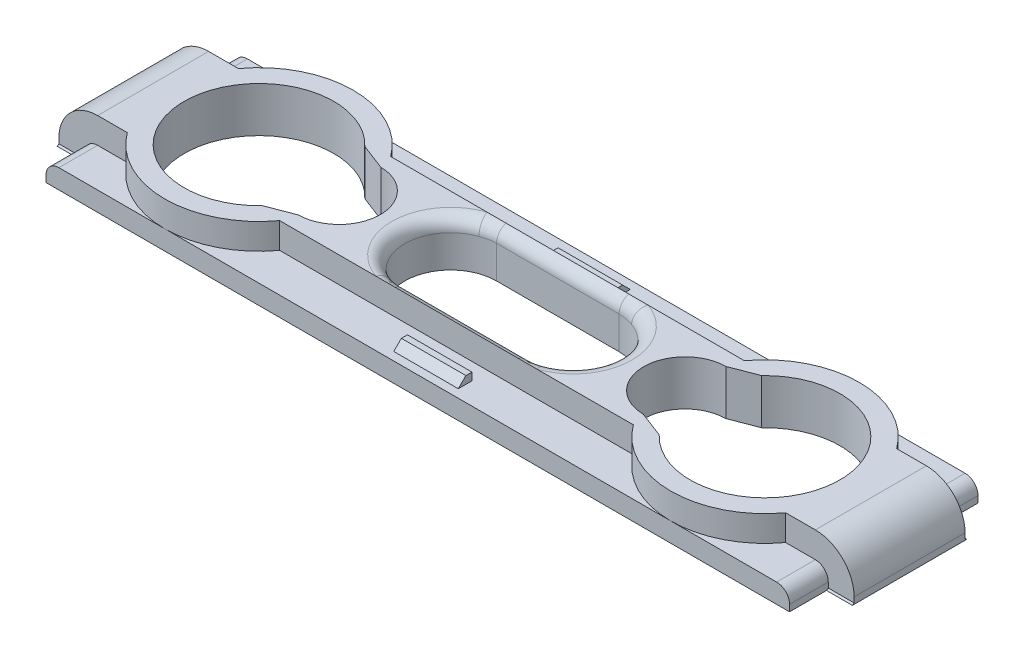
SolidWorks part; units mm, degrees
ref_plane "正面" through (0, 0, 0) normal (0, 0, 1) x (1, 0, 0)
ref_plane "平面" through (0, 0, 0) normal (0, 1, 0) x (1, 0, 0)
ref_plane "右側面" through (0, 0, 0) normal (1, 0, 0) x (0, 0, -1)
sketch "ｽｹｯﾁ2" plane through (0, 0, 0) normal (0, 0, 1) x (1, 0, 0)
  line L0 (0, 0) -> (54, 0) construction
  line L1 (0, 20) -> (54, 20) construction
  line L2 (-3.8, 47.4) -> (57.8, 47.4)
  line L3 (54, 0) -> (54, 40) construction
  line L4 (54, 40) -> (0, 40) construction
  line L5 (0, 40) -> (0, 0) construction
  line L6 (57.8, 47.4) -> (57.8, -7.4)
  line L7 (57.8, -7.4) -> (-3.8, -7.4)
  line L8 (-3.8, -7.4) -> (-3.8, 47.4)
  line L9 (27, 47.4) -> (27, -7.4) construction
  line L10 (27, 32.0981) -> (27, 34.8848) construction
  line L11 (17.3965, 32.0981) -> (17.3965, 34.8848)
  line L12 (36.6035, 32.0981) -> (36.6035, 34.8848)
  line L13 (27, 7.9019) -> (27, 5.1152) construction
  line L14 (17.3965, 7.9019) -> (17.3965, 5.1152)
  line L15 (36.6035, 7.9019) -> (36.6035, 5.1152)
  line L16 (52, 20) -> (27, 20) construction
  line L18 (46.1198, 20) -> (44.8536, 20) construction
  line L19 (52, 23.9649) -> (52, 16.0351) construction
  line L20 (46.1198, 13.1981) -> (44.8536, 13.1981)
  line L21 (46.1198, 26.8019) -> (44.8536, 26.8019)
  line L22 (7.8802, 20) -> (9.1464, 20) construction
  line L23 (7.8802, 13.1981) -> (9.1464, 13.1981)
  line L24 (7.8802, 26.8019) -> (9.1464, 26.8019)
  circle A0 centre (2, 2) radius 1.1 construction
  circle A1 centre (52, 2) radius 1.1 construction
  circle A2 centre (52, 38) radius 1.1 construction
  circle A3 centre (2, 38) radius 1.1 construction
  circle A4 centre (2, 38) radius 1.05
  circle A5 centre (2, 38) radius 1.8491
  circle A6 centre (2, 2) radius 1.8491
  circle A7 centre (52, 2) radius 1.8491
  circle A8 centre (52, 38) radius 1.8491
  circle A9 centre (52, 38) radius 1.05
  circle A10 centre (52, 2) radius 1.05
  circle A11 centre (2, 2) radius 1.05
  arc A12 (17.3965, 32.0981) -> (36.6035, 32.0981) centre (27, 32.0981) ccw
  arc A13 (36.6035, 34.8848) -> (17.3965, 34.8848) centre (27, 34.8848) ccw
  arc A14 (46.1198, 13.1981) -> (46.1198, 26.8019) centre (46.1198, 20) ccw
  arc A15 (44.8536, 26.8019) -> (44.8536, 13.1981) centre (44.8536, 20) ccw
  arc A16 (7.8802, 13.1981) -> (7.8802, 26.8019) centre (7.8802, 20) cw
  arc A17 (9.1464, 26.8019) -> (9.1464, 13.1981) centre (9.1464, 20) cw
  arc A18 (17.3965, 7.9019) -> (36.6035, 7.9019) centre (27, 7.9019) cw
  arc A19 (36.6035, 5.1152) -> (17.3965, 5.1152) centre (27, 5.1152) cw
  point P30 (27, 33.4915)
  point P41 (45.4867, 20)
  point P48 (8.5133, 20)
  point P55 (27, 6.5085)
  dimension "D3" = 2.2
  dimension "D8" = 2.1
  dimension "D9" = 30.8
  dimension "D1" = 40
  dimension "D2" = 54
  dimension "D4" = 27.4
  dimension "D5" = 27.4
extrude "ﾎﾞｽ - 押し出し1" add sketch "ｽｹｯﾁ2" along normal blind 1.5 contours L7 L8 L2 L6 | L15 A19 L14 A18 | L20 A15 L21 A14 | L11 A13 L12 A12 | A17 L23 A16 L24
extrude "ﾎﾞｽ - 押し出し3" add sketch "ｽｹｯﾁ2<4>" along normal blind 3.3 contours A7 | A6 | A5 | A8
sketch "ｽｹｯﾁ2<4>" plane through (0, 0, 0) normal (0, 0, 1) x (1, 0, 0) same geometry as "ｽｹｯﾁ2"
sketch "ｽｹｯﾁ6" plane through (-3.8, 0, 0) normal (-1, 0, 0) x (0, 0, 1)
  line L0 (1.5, -7.4) -> (0, -7.4) construction
  line L7 (1.5, -7.4) -> (1.5, 47.4) construction
  line L8 (-9.6, 33.9866) -> (-8.8, 31.9) construction
  line L9 (-5.8, 43.7) -> (-5.8, 19.9) construction
  line L12 (-13.1, 20) -> (0, 20) construction
  line L14 (-2.8, 31.9) -> (-2, 33.9866) construction
  line L15 (-9.6, 33.9866) -> (-8.8, 31.9) construction
  line L20 (-13.1, 47.4) -> (-13.1, -7.4)
  line L21 (1.5, -7.4) -> (1.5, 47.4)
  line L22 (-5.8, 23.1) -> (-5.8, 16.9) construction
  line L23 (-3.5215, 23.1) -> (-3.5215, 16.9)
  line L24 (-8.0785, 23.1) -> (-8.0785, 16.9)
  line L26 (1.5, 47.4) -> (-13.1, 47.4)
  line L27 (1.5, -7.4) -> (-13.1, -7.4)
  line L28 (-2.8, 31.9) -> (-2, 33.9866) construction
  line L29 (0, -7.4) -> (0, 47.4) construction
  line L30 (-2.8, 8.1) -> (-2, 6.0134) construction
  line L31 (-9.6, 6.0134) -> (-8.8, 8.1) construction
  line L32 (0, 16.9) -> (-11.6, 16.9) construction
  line L33 (-9.7702, 33.8718) -> (-8.9998, 31.8624)
  line L34 (-2.6002, 31.8624) -> (-1.8298, 33.8718)
  line L35 (-2.6002, 8.1376) -> (-1.8298, 6.1282)
  line L36 (-9.7702, 6.1282) -> (-8.9998, 8.1376)
  arc A3 (-2, 33.9866) -> (-9.6, 33.9866) centre (-5.8, 38.1) ccw construction
  arc A4 (-2, 33.9866) -> (-9.6, 33.9866) centre (-5.8, 38.1) ccw construction
  arc A10 (-8.8, 31.9) -> (-2.8, 31.9) centre (-5.8, 31.9) ccw construction
  arc A11 (-8.8, 31.9) -> (-2.8, 31.9) centre (-5.8, 31.9) ccw construction
  arc A12 (-3.5215, 23.1) -> (-8.0785, 23.1) centre (-5.8, 23.1) ccw
  arc A13 (-8.0785, 16.9) -> (-3.5215, 16.9) centre (-5.8, 16.9) ccw
  arc A14 (-8.8, 8.1) -> (-2.8, 8.1) centre (-5.8, 8.1) cw construction
  arc A15 (-2, 6.0134) -> (-9.6, 6.0134) centre (-5.8, 1.9) cw construction
  arc A16 (-1.8298, 33.8718) -> (-9.7702, 33.8718) centre (-5.8, 38.1) ccw
  arc A17 (-8.9998, 31.8624) -> (-2.6002, 31.8624) centre (-5.8, 31.9) ccw
  arc A18 (-8.9998, 8.1376) -> (-2.6002, 8.1376) centre (-5.8, 8.1) cw
  arc A19 (-1.8298, 6.1282) -> (-9.7702, 6.1282) centre (-5.8, 1.9) cw
  point P32 (-5.8, 20)
  dimension "D2" = 0.2
  dimension "D1" = 0
extrude "ﾎﾞｽ - 押し出し4" add sketch "ｽｹｯﾁ6" against normal up to surface (3.5 mm away)
sketch "ｽｹｯﾁ9" plane through (57.8, 0, 0) normal (1, 0, 0) x (0, 0, -1)
  line L2 (8.9998, 31.8624) -> (9.7702, 33.8718)
  line L3 (1.8298, 33.8718) -> (2.6002, 31.8624)
  line L4 (8.9998, 31.8624) -> (9.7702, 33.8718)
  line L5 (1.8298, 33.8718) -> (2.6002, 31.8624)
  line L6 (2.6002, 8.1376) -> (1.8298, 6.1282)
  line L7 (9.7702, 6.1282) -> (8.9998, 8.1376)
  line L8 (2.6002, 8.1376) -> (1.8298, 6.1282)
  line L9 (9.7702, 6.1282) -> (8.9998, 8.1376)
  line L10 (3.5215, 23.1) -> (3.5215, 16.9)
  line L11 (8.0785, 16.9) -> (8.0785, 23.1)
  line L12 (3.5215, 23.1) -> (3.5215, 16.9)
  line L13 (8.0785, 16.9) -> (8.0785, 23.1)
  line L16 (-1.5, 47.4) -> (-1.5, -7.4)
  line L17 (13.1, 47.4) -> (-1.5, 47.4)
  line L18 (13.1, -7.4) -> (13.1, 47.4)
  line L19 (-1.5, -7.4) -> (13.1, -7.4)
  line L20 (-1.5, 47.4) -> (-1.5, -7.4)
  line L21 (13.1, 47.4) -> (-1.5, 47.4)
  line L22 (13.1, -7.4) -> (13.1, 47.4)
  line L23 (-1.5, -7.4) -> (13.1, -7.4)
  arc A2 (2.6002, 31.8624) -> (8.9998, 31.8624) centre (5.8, 31.9) ccw
  arc A3 (9.7702, 33.8718) -> (1.8298, 33.8718) centre (5.8, 38.1) ccw
  arc A4 (2.6002, 31.8624) -> (8.9998, 31.8624) centre (5.8, 31.9) ccw
  arc A5 (9.7702, 33.8718) -> (1.8298, 33.8718) centre (5.8, 38.1) ccw
  arc A6 (1.8298, 6.1282) -> (9.7702, 6.1282) centre (5.8, 1.9) ccw
  arc A7 (8.9998, 8.1376) -> (2.6002, 8.1376) centre (5.8, 8.1) ccw
  arc A8 (1.8298, 6.1282) -> (9.7702, 6.1282) centre (5.8, 1.9) ccw
  arc A9 (8.9998, 8.1376) -> (2.6002, 8.1376) centre (5.8, 8.1) ccw
  arc A10 (3.5215, 16.9) -> (8.0785, 16.9) centre (5.8, 16.9) ccw
  arc A11 (8.0785, 23.1) -> (3.5215, 23.1) centre (5.8, 23.1) ccw
  arc A12 (3.5215, 16.9) -> (8.0785, 16.9) centre (5.8, 16.9) ccw
  arc A13 (8.0785, 23.1) -> (3.5215, 23.1) centre (5.8, 23.1) ccw
  dimension "D1" = 0
  dimension "D2" = 0
  dimension "D3" = 0
  dimension "D4" = 0
extrude "ﾎﾞｽ - 押し出し6" add sketch "ｽｹｯﾁ9" against normal up to surface (3.5 mm away)
sketch "ｽｹｯﾁ10" plane through (0, -7.4, 0) normal (0, -1, 0) x (1, 0, 0)
  line L0 (22.25, -5.8) -> (31.75, -5.8) construction
  line L1 (22.25, -2.25) -> (31.75, -2.25)
  line L2 (22.25, -9.35) -> (31.75, -9.35)
  line L5 (27, 1.5) -> (27, -13.1) construction
  line L10 (16.8, -5.8) -> (37.2, -5.8) construction
  line L11 (21.4, -5.8) -> (32.6, -5.8) construction
  line L13 (21.4, -2.55) -> (32.6, -2.55) construction
  line L14 (21.4, -9.05) -> (32.6, -9.05) construction
  line L17 (11.5134, -9.6) -> (13.6, -8.8)
  line L18 (57.8, 1.5) -> (57.8, -13.1) construction
  line L19 (57.8, 1.5) -> (-3.8, 1.5) construction
  line L20 (-3.8, 1.5) -> (-3.8, -13.1) construction
  line L22 (13.6, -2.8) -> (11.5134, -2)
  line L23 (57.8, 1.5) -> (57.8, -13.1)
  line L24 (57.8, 1.5) -> (-3.8, 1.5)
  line L25 (-3.8, 1.5) -> (-3.8, -13.1)
  line L27 (11.5134, -9.6) -> (13.6, -8.8) construction
  line L28 (13.6, -2.8) -> (11.5134, -2) construction
  line L29 (-3.8, -13.1) -> (57.8, -13.1)
  line L46 (11.6282, -9.7702) -> (13.6376, -8.9998)
  line L47 (13.6376, -2.6002) -> (11.6282, -1.8298)
  line L48 (40.4, -2.8) -> (42.4866, -2) construction
  line L49 (42.4866, -9.6) -> (40.4, -8.8) construction
  line L50 (40.3624, -2.6002) -> (42.3718, -1.8298)
  line L51 (42.3718, -9.7702) -> (40.3624, -8.9998)
  arc A1 (22.25, -2.25) -> (22.25, -9.35) centre (22.25, -5.8) ccw
  arc A2 (31.75, -9.35) -> (31.75, -2.25) centre (31.75, -5.8) ccw
  arc A8 (21.4, -2.55) -> (21.4, -9.05) centre (21.4, -5.8) ccw construction
  arc A9 (32.6, -9.05) -> (32.6, -2.55) centre (32.6, -5.8) ccw construction
  arc A12 (11.5134, -2) -> (11.5134, -9.6) centre (7.4, -5.8) ccw
  arc A13 (13.6, -8.8) -> (13.6, -2.8) centre (13.6, -5.8) ccw
  arc A14 (11.5134, -2) -> (11.5134, -9.6) centre (7.4, -5.8) ccw construction
  arc A15 (13.6, -8.8) -> (13.6, -2.8) centre (13.6, -5.8) ccw construction
  arc A32 (11.6282, -1.8298) -> (11.6282, -9.7702) centre (7.4, -5.8) ccw
  arc A33 (13.6376, -8.9998) -> (13.6376, -2.6002) centre (13.6, -5.8) ccw
  arc A34 (40.4, -8.8) -> (40.4, -2.8) centre (40.4, -5.8) cw construction
  arc A35 (42.4866, -2) -> (42.4866, -9.6) centre (46.6, -5.8) cw construction
  arc A36 (40.3624, -8.9998) -> (40.3624, -2.6002) centre (40.4, -5.8) cw
  arc A37 (42.3718, -1.8298) -> (42.3718, -9.7702) centre (46.6, -5.8) cw
  point P24 (27, -5.8)
  point P41 (27, -5.8)
  dimension "D1" = 0
  dimension "D4" = 11.2
  dimension "D2" = 0.2
  dimension "D3" = 6.5
extrude "ﾎﾞｽ - 押し出し7" add sketch "ｽｹｯﾁ10" against normal blind 3.5
sketch "ｽｹｯﾁ11" plane through (0, 47.4, 0) normal (0, 1, 0) x (1, 0, 0)
  line L2 (40.3624, 2.6002) -> (42.3718, 1.8298)
  line L3 (42.3718, 9.7702) -> (40.3624, 8.9998)
  line L4 (57.8, -1.5) -> (57.8, 13.1)
  line L5 (57.8, 13.1) -> (-3.8, 13.1)
  line L6 (-3.8, 13.1) -> (-3.8, -1.5)
  line L7 (-3.8, -1.5) -> (57.8, -1.5)
  line L8 (57.8, -1.5) -> (57.8, 13.1)
  line L9 (57.8, 13.1) -> (-3.8, 13.1)
  line L10 (-3.8, 13.1) -> (-3.8, -1.5)
  line L11 (-3.8, -1.5) -> (57.8, -1.5)
  line L12 (40.3624, 2.6002) -> (42.3718, 1.8298)
  line L13 (42.3718, 9.7702) -> (40.3624, 8.9998)
  line L14 (13.6376, 8.9998) -> (11.6282, 9.7702)
  line L15 (11.6282, 1.8298) -> (13.6376, 2.6002)
  line L16 (13.6376, 8.9998) -> (11.6282, 9.7702)
  line L17 (11.6282, 1.8298) -> (13.6376, 2.6002)
  line L18 (22.25, 2.25) -> (31.75, 2.25)
  line L19 (31.75, 9.35) -> (22.25, 9.35)
  line L20 (22.25, 2.25) -> (31.75, 2.25)
  line L21 (31.75, 9.35) -> (22.25, 9.35)
  arc A2 (42.3718, 1.8298) -> (42.3718, 9.7702) centre (46.6, 5.8) ccw
  arc A3 (40.3624, 8.9998) -> (40.3624, 2.6002) centre (40.4, 5.8) ccw
  arc A4 (42.3718, 1.8298) -> (42.3718, 9.7702) centre (46.6, 5.8) ccw
  arc A5 (40.3624, 8.9998) -> (40.3624, 2.6002) centre (40.4, 5.8) ccw
  arc A6 (13.6376, 2.6002) -> (13.6376, 8.9998) centre (13.6, 5.8) ccw
  arc A7 (11.6282, 9.7702) -> (11.6282, 1.8298) centre (7.4, 5.8) ccw
  arc A8 (13.6376, 2.6002) -> (13.6376, 8.9998) centre (13.6, 5.8) ccw
  arc A9 (11.6282, 9.7702) -> (11.6282, 1.8298) centre (7.4, 5.8) ccw
  arc A10 (31.75, 2.25) -> (31.75, 9.35) centre (31.75, 5.8) ccw
  arc A11 (22.25, 9.35) -> (22.25, 2.25) centre (22.25, 5.8) ccw
  arc A12 (31.75, 2.25) -> (31.75, 9.35) centre (31.75, 5.8) ccw
  arc A13 (22.25, 9.35) -> (22.25, 2.25) centre (22.25, 5.8) ccw
  dimension "D1" = 0
  dimension "D2" = 0
  dimension "D3" = 0
  dimension "D4" = 0
extrude "ﾎﾞｽ - 押し出し8" add sketch "ｽｹｯﾁ11" against normal blind 3.5
fillet "ﾌｨﾚｯﾄ1" radius 3 4 edges at (-3.8, -7.4, -5.8) (57.8, -7.4, -5.8) (57.8, 47.4, -5.8) (-3.8, 47.4, -5.8)
sketch "ｽｹｯﾁ12" plane through (0, 0, -13.1) normal (0, 0, -1) x (-1, 0, 0)
  line L1 (-55.8, 44.4) -> (-55.8, -4.4)
  line L2 (-54.8, -5.4) -> (0.8, -5.4)
  line L3 (1.8, -4.4) -> (1.8, 44.4)
  line L4 (-54.8, -7.4) -> (0.8, -7.4)
  line L5 (3.8, -4.4) -> (3.8, 44.4)
  line L6 (-54.8, -7.4) -> (0.8, -7.4)
  line L7 (-57.8, 44.4) -> (-57.8, -4.4)
  line L8 (0.8, 47.4) -> (-54.8, 47.4)
  line L9 (3.8, -4.4) -> (3.8, 44.4)
  line L10 (0.8, 47.4) -> (-54.8, 47.4)
  line L11 (-57.8, 44.4) -> (-57.8, -4.4)
  line L12 (0.8, 45.4) -> (-54.8, 45.4)
  line L16 (-57.8, 44.4) -> (-57.8, -4.4) construction
  line L17 (-54.8, -7.4) -> (0.8, -7.4) construction
  line L18 (0.8, 47.4) -> (-54.8, 47.4) construction
  arc A0 (-54.8, 45.4) -> (-55.8, 44.4) centre (-54.8, 44.4) ccw
  arc A1 (-55.8, -4.4) -> (-54.8, -5.4) centre (-54.8, -4.4) ccw
  arc A2 (0.8, -5.4) -> (1.8, -4.4) centre (0.8, -4.4) ccw
  arc A3 (1.8, 44.4) -> (0.8, 45.4) centre (0.8, 44.4) ccw
  arc A4 (0.8, -7.4) -> (3.8, -4.4) centre (0.8, -4.4) ccw
  arc A5 (3.8, 44.4) -> (0.8, 47.4) centre (0.8, 44.4) ccw
  arc A6 (-54.8, 47.4) -> (-57.8, 44.4) centre (-54.8, 44.4) ccw
  arc A7 (-57.8, -4.4) -> (-54.8, -7.4) centre (-54.8, -4.4) ccw
  arc A8 (0.8, -7.4) -> (3.8, -4.4) centre (0.8, -4.4) ccw
  arc A9 (3.8, 44.4) -> (0.8, 47.4) centre (0.8, 44.4) ccw
  arc A10 (-54.8, 47.4) -> (-57.8, 44.4) centre (-54.8, 44.4) ccw
  arc A11 (-57.8, -4.4) -> (-54.8, -7.4) centre (-54.8, -4.4) ccw
  dimension "D1" = 0
  dimension "D2" = 2
extrude "ｶｯﾄ - 押し出し1" cut sketch "ｽｹｯﾁ12" against normal blind 3
sketch "ｽｹｯﾁ22" plane through (0, 0, 1.5) normal (0, 0, 1) x (1, 0, 0)
  line L0 (-1.8, 44.4) -> (-1.8, -4.4)
  line L1 (-0.8, -5.4) -> (54.8, -5.4)
  line L2 (55.8, -4.4) -> (55.8, 44.4)
  line L3 (54.8, 45.4) -> (-0.8, 45.4)
  line L4 (-3.8, 44.4) -> (-3.8, -4.4)
  line L5 (-0.8, -7.4) -> (54.8, -7.4)
  line L6 (57.8, -4.4) -> (57.8, 44.4)
  line L7 (54.8, 47.4) -> (-0.8, 47.4)
  line L8 (-3.8, 44.4) -> (-3.8, -4.4)
  line L9 (-0.8, -7.4) -> (54.8, -7.4)
  line L10 (57.8, -4.4) -> (57.8, 44.4)
  line L11 (54.8, 47.4) -> (-0.8, 47.4)
  arc A0 (-1.8, -4.4) -> (-0.8, -5.4) centre (-0.8, -4.4) ccw
  arc A1 (54.8, -5.4) -> (55.8, -4.4) centre (54.8, -4.4) ccw
  arc A2 (55.8, 44.4) -> (54.8, 45.4) centre (54.8, 44.4) ccw
  arc A3 (-0.8, 45.4) -> (-1.8, 44.4) centre (-0.8, 44.4) ccw
  arc A4 (-3.8, -4.4) -> (-0.8, -7.4) centre (-0.8, -4.4) ccw
  arc A5 (54.8, -7.4) -> (57.8, -4.4) centre (54.8, -4.4) ccw
  arc A6 (57.8, 44.4) -> (54.8, 47.4) centre (54.8, 44.4) ccw
  arc A7 (-0.8, 47.4) -> (-3.8, 44.4) centre (-0.8, 44.4) ccw
  arc A8 (-3.8, -4.4) -> (-0.8, -7.4) centre (-0.8, -4.4) ccw
  arc A9 (54.8, -7.4) -> (57.8, -4.4) centre (54.8, -4.4) ccw
  arc A10 (57.8, 44.4) -> (54.8, 47.4) centre (54.8, 44.4) ccw
  arc A11 (-0.8, 47.4) -> (-3.8, 44.4) centre (-0.8, 44.4) ccw
  dimension "D1" = 0
  dimension "D2" = 2
extrude "ｶｯﾄ - 押し出し2" cut sketch "ｽｹｯﾁ22" against normal blind 3
sketch "ｽｹｯﾁ21" plane through (0, -7.4, 0) normal (0, -1, 0) x (1, 0, 0)
  line L0 (-0.8, -5.8) -> (-7.911, -5.8) construction
  line L1 (11.2923, -1.5) -> (42.7077, -1.5) construction
  line L5 (1.5008, -10.1) -> (3.5077, -10.1)
  line L6 (-0.8, -1.5) -> (3.5077, -1.5) construction
  line L10 (11.2923, -1.5) -> (13.2992, -1.5)
  line L11 (-0.8, -1.5) -> (-0.8, -10.1) construction
  line L12 (1.5008, -1.5) -> (3.5077, -1.5)
  line L19 (11.2923, -10.1) -> (13.2992, -10.1)
  line L23 (27, 1.5) -> (27, 9.2892) construction
  line L24 (-0.8, 1.5) -> (54.8, 1.5) construction
  line L25 (42.7077, -10.1) -> (40.7008, -10.1)
  line L26 (52.4992, -1.5) -> (50.4923, -1.5)
  line L27 (42.7077, -1.5) -> (40.7008, -1.5)
  line L28 (52.4992, -10.1) -> (50.4923, -10.1)
  arc A6 (13.2992, -10.1) -> (1.5008, -10.1) centre (7.4, -5.8) cw
  arc A10 (11.2923, -1.5) -> (3.5077, -1.5) centre (7.4, -5.8) ccw construction
  arc A13 (11.2923, -1.5) -> (3.5077, -1.5) centre (7.4, -5.8) ccw
  arc A14 (13.2992, -1.5) -> (1.5008, -1.5) centre (7.4, -5.8) ccw
  arc A25 (12.2989, -0.3879) -> (2.5011, -0.3879) centre (7.4, -5.8) ccw construction
  arc A26 (11.2923, -10.1) -> (3.5077, -10.1) centre (7.4, -5.8) cw
  arc A27 (42.7077, -10.1) -> (50.4923, -10.1) centre (46.6, -5.8) ccw
  arc A28 (40.7008, -1.5) -> (52.4992, -1.5) centre (46.6, -5.8) cw
  arc A29 (42.7077, -1.5) -> (50.4923, -1.5) centre (46.6, -5.8) cw
  arc A30 (40.7008, -10.1) -> (52.4992, -10.1) centre (46.6, -5.8) ccw
  dimension "D1" = 1.5
extrude "ﾎﾞｽ - 押し出し9" add sketch "ｽｹｯﾁ21" against normal up to surface (2 mm away) up to face at (27, -5.4, -0.375)
sketch "ｽｹｯﾁ23" plane through (0, 47.4, 0) normal (0, 1, 0) x (1, 0, 0)
  line L2 (1.5008, 10.1) -> (3.5077, 10.1)
  line L3 (11.2923, 10.1) -> (13.2992, 10.1)
  line L4 (1.5008, 10.1) -> (3.5077, 10.1)
  line L5 (11.2923, 10.1) -> (13.2992, 10.1)
  line L6 (52.4992, 1.5) -> (50.4923, 1.5)
  line L7 (42.7077, 1.5) -> (40.7008, 1.5)
  line L8 (52.4992, 1.5) -> (50.4923, 1.5)
  line L9 (42.7077, 1.5) -> (40.7008, 1.5)
  line L10 (40.7008, 10.1) -> (42.7077, 10.1)
  line L11 (50.4923, 10.1) -> (52.4992, 10.1)
  line L12 (40.7008, 10.1) -> (42.7077, 10.1)
  line L13 (50.4923, 10.1) -> (52.4992, 10.1)
  line L14 (13.2992, 1.5) -> (11.2923, 1.5)
  line L15 (3.5077, 1.5) -> (1.5008, 1.5)
  line L16 (13.2992, 1.5) -> (11.2923, 1.5)
  line L17 (3.5077, 1.5) -> (1.5008, 1.5)
  arc A2 (11.2923, 10.1) -> (3.5077, 10.1) centre (7.4, 5.8) ccw
  arc A3 (13.2992, 10.1) -> (1.5008, 10.1) centre (7.4, 5.8) ccw
  arc A4 (11.2923, 10.1) -> (3.5077, 10.1) centre (7.4, 5.8) ccw
  arc A5 (13.2992, 10.1) -> (1.5008, 10.1) centre (7.4, 5.8) ccw
  arc A6 (42.7077, 1.5) -> (50.4923, 1.5) centre (46.6, 5.8) ccw
  arc A7 (40.7008, 1.5) -> (52.4992, 1.5) centre (46.6, 5.8) ccw
  arc A8 (42.7077, 1.5) -> (50.4923, 1.5) centre (46.6, 5.8) ccw
  arc A9 (40.7008, 1.5) -> (52.4992, 1.5) centre (46.6, 5.8) ccw
  arc A10 (52.4992, 10.1) -> (40.7008, 10.1) centre (46.6, 5.8) ccw
  arc A11 (50.4923, 10.1) -> (42.7077, 10.1) centre (46.6, 5.8) ccw
  arc A12 (52.4992, 10.1) -> (40.7008, 10.1) centre (46.6, 5.8) ccw
  arc A13 (50.4923, 10.1) -> (42.7077, 10.1) centre (46.6, 5.8) ccw
  arc A14 (1.5008, 1.5) -> (13.2992, 1.5) centre (7.4, 5.8) ccw
  arc A15 (3.5077, 1.5) -> (11.2923, 1.5) centre (7.4, 5.8) ccw
  arc A16 (1.5008, 1.5) -> (13.2992, 1.5) centre (7.4, 5.8) ccw
  arc A17 (3.5077, 1.5) -> (11.2923, 1.5) centre (7.4, 5.8) ccw
  dimension "D1" = 0
  dimension "D2" = 0
  dimension "D3" = 0
  dimension "D4" = 0
extrude "ﾎﾞｽ - 押し出し10" add sketch "ｽｹｯﾁ23" against normal up to surface (2 mm away) up to face at (27, 45.4, -11.225)
sketch "ｽｹｯﾁ24" plane through (57.8, 0, 0) normal (1, 0, 0) x (0, 0, -1)
  line L0 (1.5, 5.7923) -> (1.5, 34.2077) construction
  line L1 (1.5, 41.9923) -> (1.5, 44.4) construction
  line L3 (1.5, 41.9923) -> (1.5, 43.9992)
  line L4 (1.5, 32.2008) -> (1.5, 34.2077)
  line L7 (5.8, 44.4) -> (5.8, 52.6929) construction
  line L8 (10.1, 44.4) -> (1.5, 44.4) construction
  line L9 (10.1, 32.2008) -> (10.1, 34.2077)
  line L10 (10.1, 41.9923) -> (10.1, 43.9992)
  line L11 (-1.5, 20) -> (-9.7166, 20) construction
  line L15 (-1.5, -4.4) -> (-1.5, 44.4) construction
  line L22 (10.1, -1.9923) -> (10.1, -3.9992)
  line L23 (10.1, 7.7992) -> (10.1, 5.7923)
  line L24 (1.5, 7.7992) -> (1.5, 5.7923)
  line L25 (1.5, -1.9923) -> (1.5, -3.9992)
  arc A0 (1.5, 43.9992) -> (1.5, 32.2008) centre (5.8, 38.1) ccw
  arc A1 (0.3879, 42.9989) -> (0.3879, 33.2011) centre (5.8, 38.1) ccw construction
  arc A7 (1.5, 41.9923) -> (1.5, 34.2077) centre (5.8, 38.1) ccw construction
  arc A11 (1.5, 41.9923) -> (1.5, 34.2077) centre (5.8, 38.1) ccw
  arc A12 (10.1, 43.9992) -> (10.1, 32.2008) centre (5.8, 38.1) cw
  arc A13 (10.1, -3.9992) -> (10.1, 7.7992) centre (5.8, 1.9) ccw
  arc A14 (1.5, -1.9923) -> (1.5, 5.7923) centre (5.8, 1.9) cw
  arc A15 (1.5, -3.9992) -> (1.5, 7.7992) centre (5.8, 1.9) cw
  arc A16 (10.1, 34.2077) -> (10.1, 41.9923) centre (5.8, 38.1) ccw construction
  arc A17 (10.1, -1.9923) -> (10.1, 5.7923) centre (5.8, 1.9) ccw construction
  arc A18 (10.1, 34.2077) -> (10.1, 41.9923) centre (5.8, 38.1) ccw
  arc A19 (10.1, -1.9923) -> (10.1, 5.7923) centre (5.8, 1.9) ccw
  dimension "D1" = 1.5
extrude "ﾎﾞｽ - 押し出し11" add sketch "ｽｹｯﾁ24" against normal up to surface (2 mm away) up to face at (55.8, 20, -0.375)
sketch "ｽｹｯﾁ25" plane through (-3.8, 0, 0) normal (-1, 0, 0) x (0, 0, 1)
  line L2 (-1.5, 43.9992) -> (-1.5, 41.9923)
  line L3 (-1.5, 34.2077) -> (-1.5, 32.2008)
  line L4 (-1.5, 43.9992) -> (-1.5, 41.9923)
  line L5 (-1.5, 34.2077) -> (-1.5, 32.2008)
  line L6 (-1.5, 7.7992) -> (-1.5, 5.7923)
  line L7 (-1.5, -1.9923) -> (-1.5, -3.9992)
  line L8 (-1.5, 7.7992) -> (-1.5, 5.7923)
  line L9 (-1.5, -1.9923) -> (-1.5, -3.9992)
  line L10 (-10.1, -3.9992) -> (-10.1, -1.9923)
  line L11 (-10.1, 5.7923) -> (-10.1, 7.7992)
  line L12 (-10.1, -3.9992) -> (-10.1, -1.9923)
  line L13 (-10.1, 5.7923) -> (-10.1, 7.7992)
  line L14 (-10.1, 32.2008) -> (-10.1, 34.2077)
  line L15 (-10.1, 41.9923) -> (-10.1, 43.9992)
  line L16 (-10.1, 32.2008) -> (-10.1, 34.2077)
  line L17 (-10.1, 41.9923) -> (-10.1, 43.9992)
  arc A2 (-1.5, 32.2008) -> (-1.5, 43.9992) centre (-5.8, 38.1) ccw
  arc A3 (-1.5, 34.2077) -> (-1.5, 41.9923) centre (-5.8, 38.1) ccw
  arc A4 (-1.5, 32.2008) -> (-1.5, 43.9992) centre (-5.8, 38.1) ccw
  arc A5 (-1.5, 34.2077) -> (-1.5, 41.9923) centre (-5.8, 38.1) ccw
  arc A6 (-1.5, -1.9923) -> (-1.5, 5.7923) centre (-5.8, 1.9) ccw
  arc A7 (-1.5, -3.9992) -> (-1.5, 7.7992) centre (-5.8, 1.9) ccw
  arc A8 (-1.5, -1.9923) -> (-1.5, 5.7923) centre (-5.8, 1.9) ccw
  arc A9 (-1.5, -3.9992) -> (-1.5, 7.7992) centre (-5.8, 1.9) ccw
  arc A10 (-10.1, 7.7992) -> (-10.1, -3.9992) centre (-5.8, 1.9) ccw
  arc A11 (-10.1, 5.7923) -> (-10.1, -1.9923) centre (-5.8, 1.9) ccw
  arc A12 (-10.1, 7.7992) -> (-10.1, -3.9992) centre (-5.8, 1.9) ccw
  arc A13 (-10.1, 5.7923) -> (-10.1, -1.9923) centre (-5.8, 1.9) ccw
  arc A14 (-10.1, 43.9992) -> (-10.1, 32.2008) centre (-5.8, 38.1) ccw
  arc A15 (-10.1, 41.9923) -> (-10.1, 34.2077) centre (-5.8, 38.1) ccw
  arc A16 (-10.1, 43.9992) -> (-10.1, 32.2008) centre (-5.8, 38.1) ccw
  arc A17 (-10.1, 41.9923) -> (-10.1, 34.2077) centre (-5.8, 38.1) ccw
  dimension "D1" = 0
  dimension "D2" = 0
  dimension "D3" = 0
  dimension "D4" = 0
extrude "ﾎﾞｽ - 押し出し12" add sketch "ｽｹｯﾁ25" against normal up to surface (2 mm away) up to face at (-1.8, 20, -11.225)
ref_plane "平面1" through (0, 20, 0) normal (0, 1, 0) x (1, 0, 0)
sketch "ｽｹｯﾁ26" plane through (0, 20, 0) normal (0, 1, 0) x (1, 0, 0)
  line L1 (-1.8, 13.1) -> (55.8, 13.1) construction
  line L2 (56.3887, -0.2466) -> (56.3887, 0.2234)
  line L3 (55.8, -0.8353) -> (56.3887, -0.2466)
  line L4 (55.8, 0.2234) -> (55.8, -0.8353)
  line L5 (27, 13.1) -> (27, 21.7666) construction
  line L6 (55.8, 0.2234) -> (56.3887, 0.2234)
  line L7 (57.8, 5.8) -> (54.8, 5.8) construction
  line L8 (57.8, 10.1) -> (57.8, 1.5) construction
  line L9 (54.8, 1.5) -> (54.8, 10.1) construction
  line L10 (55.8, 11.3766) -> (56.3887, 11.3766)
  line L11 (55.8, 11.3766) -> (55.8, 12.4353)
  line L12 (55.8, 12.4353) -> (56.3887, 11.8466)
  line L13 (56.3887, 11.8466) -> (56.3887, 11.3766)
  line L14 (-2.3887, 11.8466) -> (-2.3887, 11.3766)
  line L15 (-1.8, 12.4353) -> (-2.3887, 11.8466)
  line L16 (-1.8, 11.3766) -> (-1.8, 12.4353)
  line L17 (-1.8, 11.3766) -> (-2.3887, 11.3766)
  line L18 (-1.8, 0.2234) -> (-2.3887, 0.2234)
  line L19 (-1.8, 0.2234) -> (-1.8, -0.8353)
  line L20 (-1.8, -0.8353) -> (-2.3887, -0.2466)
  line L21 (-2.3887, -0.2466) -> (-2.3887, 0.2234)
extrude "ﾎﾞｽ - 押し出し13" add sketch "ｽｹｯﾁ26" along normal mid plane 5
ref_plane "平面3" through (27, 0, 0) normal (-1, 0, 0) x (0, 0, 1)
sketch "ｽｹｯﾁ27" plane through (27, 0, 0) normal (-1, 0, 0) x (0, 0, 1)
  line L0 (0.2713, 45.9887) -> (-0.1987, 45.9887)
  line L1 (0.86, 45.4) -> (0.2713, 45.9887)
  line L2 (-0.1987, 45.4) -> (0.86, 45.4)
  line L3 (-1.5, -5.4) -> (1.5, -5.4) construction
  line L4 (-5.8, 47.4) -> (-5.8, 44.4) construction
  line L5 (-1.5, 45.4) -> (1.5, 45.4) construction
  line L6 (-1.5, -5.4) -> (1.5, -5.4) construction
  line L7 (1.5, 45.4) -> (1.5, -5.4) construction
  line L8 (1.5, 20) -> (10.2973, 20) construction
  line L9 (-0.1987, 45.9887) -> (-0.1987, 45.4)
  line L10 (-1.5, 47.4) -> (-10.1, 47.4) construction
  line L11 (-10.1, 44.4) -> (-1.5, 44.4) construction
  line L12 (-11.4013, 45.4) -> (-12.46, 45.4)
  line L13 (-12.46, 45.4) -> (-11.8713, 45.9887)
  line L14 (-11.8713, 45.9887) -> (-11.4013, 45.9887)
  line L15 (-11.4013, 45.4) -> (-11.4013, 45.9887)
  line L16 (-11.4013, -5.4) -> (-11.4013, -5.9887)
  line L17 (-11.8713, -5.9887) -> (-11.4013, -5.9887)
  line L18 (-12.46, -5.4) -> (-11.8713, -5.9887)
  line L19 (-11.4013, -5.4) -> (-12.46, -5.4)
  line L20 (-0.1987, -5.9887) -> (-0.1987, -5.4)
  line L21 (-0.1987, -5.4) -> (0.86, -5.4)
  line L22 (0.86, -5.4) -> (0.2713, -5.9887)
  line L23 (0.2713, -5.9887) -> (-0.1987, -5.9887)
extrude "ﾎﾞｽ - 押し出し14" add sketch "ｽｹｯﾁ27" along normal mid plane 5
ref_plane "平面4" through (0, 0, 2.9) normal (0, 0, 1) x (1, 0, 0)
sketch "ｽｹｯﾁ28" plane through (0, 0, 1.5) normal (0, 0, 1) x (1, 0, 0)
  line L0 (0, 0) -> (54, 0) construction
  line L1 (27, 20) -> (-13.2669, 20) construction
  line L2 (-0.05, 14) -> (-1.8, 14)
  line L3 (54, 0) -> (54, 40) construction
  line L4 (54, 40) -> (0, 40) construction
  line L5 (0, 40) -> (0, 0) construction
  line L6 (-1.8, 38.1) -> (-1.8, 1.9) construction
  line L7 (-1.8, 14) -> (-1.8, 26)
  line L8 (-0.05, 26) -> (-0.05, 14)
  line L9 (27, 47.4) -> (27, -7.4) construction
  line L10 (55.8, 26) -> (54.05, 26)
  line L11 (54.05, 26) -> (54.05, 14)
  line L12 (55.8, 14) -> (55.8, 26)
  line L13 (54.05, 14) -> (55.8, 14)
  line L14 (4.35, 42.5) -> (4.35, 40)
  line L15 (4.35, 42.5) -> (7.35, 42.5)
  line L16 (7.35, 42.5) -> (7.35, 40)
  line L17 (4.35, 40) -> (7.35, 40)
  line L18 (4.35, 0) -> (7.35, 0)
  line L19 (7.35, -2.5) -> (7.35, 0)
  line L20 (4.35, -2.5) -> (7.35, -2.5)
  line L21 (4.35, -2.5) -> (4.35, 0)
  line L22 (49.65, -2.5) -> (49.65, 0)
  line L23 (49.65, -2.5) -> (46.65, -2.5)
  line L24 (46.65, -2.5) -> (46.65, 0)
  line L25 (49.65, 0) -> (46.65, 0)
  line L26 (49.65, 40) -> (46.65, 40)
  line L27 (46.65, 42.5) -> (46.65, 40)
  line L28 (49.65, 42.5) -> (46.65, 42.5)
  line L29 (49.65, 42.5) -> (49.65, 40)
  line L30 (-1.8, 26) -> (-0.05, 26)
  circle A21 centre (2, 38) radius 1.8491
  circle A22 centre (2, 38) radius 1.8491 construction
  dimension "D7" = 3
  dimension "D2" = 0.1
  dimension "D6" = 2.35
  dimension "D8" = 2.5
  dimension "D1" = 0
extrude "ﾎﾞｽ - 押し出し15" add sketch "ｽｹｯﾁ28" along normal blind 3.8
sketch "ｽｹｯﾁ29" plane through (0, 0, 5.3) normal (0, 0, 1) x (1, 0, 0)
  line L0 (4.35, 39.3) -> (7.35, 39.3)
  line L1 (7.35, 42.5) -> (7.35, 39.3)
  line L2 (4.35, 42.5) -> (4.35, 39.3)
  line L3 (7.35, 42.5) -> (4.35, 42.5) construction
  line L4 (7.35, 42.5) -> (4.35, 42.5)
  line L5 (-3.8, 20) -> (-15.3419, 20) construction
  line L6 (-3.8, 32.2008) -> (-3.8, 7.7992) construction
  line L7 (7.35, -2.5) -> (4.35, -2.5)
  line L8 (4.35, -2.5) -> (4.35, 0.7)
  line L9 (7.35, -2.5) -> (7.35, 0.7)
  line L11 (4.35, 0.7) -> (7.35, 0.7)
  line L12 (27, 45.4) -> (27, 55.9669) construction
  line L13 (46.6, 45.4) -> (7.4, 45.4) construction
  line L14 (49.65, 0.7) -> (46.65, 0.7)
  line L16 (46.65, -2.5) -> (46.65, 0.7)
  line L17 (49.65, -2.5) -> (49.65, 0.7)
  line L18 (46.65, -2.5) -> (49.65, -2.5)
  line L19 (46.65, 42.5) -> (49.65, 42.5)
  line L20 (49.65, 42.5) -> (49.65, 39.3)
  line L21 (46.65, 42.5) -> (46.65, 39.3)
  line L22 (49.65, 39.3) -> (46.65, 39.3)
extrude "ﾎﾞｽ - 押し出し16" add sketch "ｽｹｯﾁ29" along normal blind 1
sketch "ｽｹｯﾁ30" plane through (0, 0, 1.5) normal (0, 0, 1) x (1, 0, 0)
  line L0 (4.35, 42.5) -> (4.35, 34.5)
  line L1 (7.35, 42.5) -> (7.35, 34.5)
  line L2 (7.85, 43) -> (7.85, 34.5)
  line L3 (7.85, 43) -> (3.85, 43)
  line L4 (7.35, 42.5) -> (4.35, 42.5)
  line L5 (4.35, 42.5) -> (4.35, 39.3)
  line L6 (4.35, 39.3) -> (7.35, 39.3)
  line L7 (7.35, 39.3) -> (7.35, 42.5)
  line L8 (7.35, 42.5) -> (4.35, 42.5)
  line L9 (3.85, 43) -> (3.85, 34.5)
  line L10 (3.85, 34.5) -> (4.35, 34.5)
  line L11 (7.35, 34.5) -> (7.85, 34.5)
  line L12 (-3.8, 20) -> (-12.0524, 20) construction
  line L14 (-3.8, 32.2008) -> (-3.8, 7.7992) construction
  line L15 (7.35, 5.5) -> (7.85, 5.5)
  line L16 (3.85, 5.5) -> (4.35, 5.5)
  line L17 (3.85, -3) -> (3.85, 5.5)
  line L18 (7.35, -2.5) -> (4.35, -2.5)
  line L19 (7.85, -3) -> (3.85, -3)
  line L20 (7.85, -3) -> (7.85, 5.5)
  line L21 (7.35, -2.5) -> (7.35, 5.5)
  line L22 (4.35, -2.5) -> (4.35, 5.5)
  line L24 (27, 47.4) -> (27, 61.077) construction
  line L25 (40.7008, 47.4) -> (13.2992, 47.4) construction
  line L26 (49.65, -2.5) -> (49.65, 5.5)
  line L27 (46.65, -2.5) -> (46.65, 5.5)
  line L28 (46.15, -3) -> (46.15, 5.5)
  line L29 (46.15, -3) -> (50.15, -3)
  line L30 (46.65, -2.5) -> (49.65, -2.5)
  line L31 (50.15, -3) -> (50.15, 5.5)
  line L32 (50.15, 5.5) -> (49.65, 5.5)
  line L33 (46.65, 5.5) -> (46.15, 5.5)
  line L34 (46.65, 34.5) -> (46.15, 34.5)
  line L35 (50.15, 34.5) -> (49.65, 34.5)
  line L36 (50.15, 43) -> (50.15, 34.5)
  line L37 (46.65, 42.5) -> (49.65, 42.5)
  line L38 (46.15, 43) -> (50.15, 43)
  line L39 (46.15, 43) -> (46.15, 34.5)
  line L40 (46.65, 42.5) -> (46.65, 34.5)
  line L41 (49.65, 42.5) -> (49.65, 34.5)
  dimension "D2" = 8
  dimension "D3" = 0.5
  dimension "D1" = 0
extrude "ｶｯﾄ - 押し出し4" cut sketch "ｽｹｯﾁ30" against normal up to vertex up to point (-0.3, -3.9, 0)
sketch "ｽｹｯﾁ31" plane through (0, 0, 0) normal (0, 0, -1) x (-1, 0, 0)
  line L4 (0.3, -3.9) -> (0.3, 1.9)
  line L5 (0.3, 43.9) -> (-7.4, 43.9)
  line L6 (-54.3, 1.9) -> (-54.3, -3.9)
  line L7 (-54.3, -3.9) -> (-46.6, -3.9)
  line L8 (0.3, -3.9) -> (0.3, 1.9)
  line L9 (0.3, 43.9) -> (-7.4, 43.9)
  line L10 (-54.3, 1.9) -> (-54.3, -3.9)
  line L11 (-54.3, -3.9) -> (-46.6, -3.9)
  line L18 (-17.3965, 34.8848) -> (-17.3965, 32.0981)
  line L19 (-17.3965, 34.8848) -> (-17.3965, 32.0981)
  line L20 (-36.6035, 32.0981) -> (-36.6035, 34.8848)
  line L21 (-36.6035, 32.0981) -> (-36.6035, 34.8848)
  line L22 (-7.4, 43.9) -> (-23.6902, 43.9)
  line L23 (-7.4, 43.9) -> (-23.6902, 43.9)
  line L24 (-36.6035, 5.1152) -> (-36.6035, 7.9019)
  line L25 (-36.6035, 5.1152) -> (-36.6035, 7.9019)
  line L26 (-17.3965, 7.9019) -> (-17.3965, 5.1152)
  line L27 (-17.3965, 7.9019) -> (-17.3965, 5.1152)
  line L28 (-7.4, -3.9) -> (0.3, -3.9)
  line L29 (-7.4, -3.9) -> (0.3, -3.9)
  line L32 (0.3, 38.1) -> (0.3, 43.9)
  line L33 (0.3, 38.1) -> (0.3, 43.9)
  line L34 (0.3, 1.9) -> (0.3, 38.1)
  line L35 (0.3, 1.9) -> (0.3, 38.1)
  line L38 (-54.3, 38.1) -> (-54.3, 1.9)
  line L39 (-54.3, 38.1) -> (-54.3, 1.9)
  line L40 (-30.3098, 43.9) -> (-46.6, 43.9)
  line L41 (-30.3098, 43.9) -> (-46.6, 43.9)
  line L43 (-23.6902, -3.9) -> (-7.4, -3.9)
  line L44 (-23.6902, -3.9) -> (-7.4, -3.9)
  line L46 (-46.6, -3.9) -> (-30.3098, -3.9)
  line L47 (-46.6, -3.9) -> (-30.3098, -3.9)
  line L50 (-46.6, 43.9) -> (-54.3, 43.9)
  line L51 (-46.6, 43.9) -> (-54.3, 43.9)
  line L52 (-54.3, 43.9) -> (-54.3, 38.1)
  line L53 (-54.3, 43.9) -> (-54.3, 38.1)
  arc A6 (-17.3965, 34.8848) -> (-23.6902, 43.9) centre (-27, 34.8848) ccw
  arc A7 (-17.3965, 34.8848) -> (-23.6902, 43.9) centre (-27, 34.8848) ccw
  arc A8 (-36.6035, 32.0981) -> (-17.3965, 32.0981) centre (-27, 32.0981) ccw
  arc A9 (-36.6035, 32.0981) -> (-17.3965, 32.0981) centre (-27, 32.0981) ccw
  arc A10 (-30.3098, 43.9) -> (-36.6035, 34.8848) centre (-27, 34.8848) ccw
  arc A11 (-30.3098, 43.9) -> (-36.6035, 34.8848) centre (-27, 34.8848) ccw
  arc A12 (-36.6035, 5.1152) -> (-30.3098, -3.9) centre (-27, 5.1152) ccw
  arc A13 (-36.6035, 5.1152) -> (-30.3098, -3.9) centre (-27, 5.1152) ccw
  arc A14 (-17.3965, 7.9019) -> (-36.6035, 7.9019) centre (-27, 7.9019) ccw
  arc A15 (-17.3965, 7.9019) -> (-36.6035, 7.9019) centre (-27, 7.9019) ccw
  arc A16 (-23.6902, -3.9) -> (-17.3965, 5.1152) centre (-27, 5.1152) ccw
  arc A17 (-23.6902, -3.9) -> (-17.3965, 5.1152) centre (-27, 5.1152) ccw
  dimension "D1" = 0
extrude "ｶｯﾄ - 押し出し5" cut sketch "ｽｹｯﾁ31" against normal blind 0.2
fillet "ﾌｨﾚｯﾄ2" radius 2 4 edges at (48.15, 40, 1.5) (48.15, 0, 1.5) (5.85, 0, 1.5) (5.85, 40, 1.5)
fillet "ﾌｨﾚｯﾄ3" radius 1.2 2 edges at (-0.05, 20, 1.5) (54.05, 20, 1.5)
fillet "ﾌｨﾚｯﾄ4" radius 1 4 edges at (18.7, 47.4, -5.8) (35.3, 47.4, -5.8) (18.7, -7.4, -5.8) (35.3, -7.4, -5.8)
sketch "ｽｹｯﾁ32" plane through (0, 0, -13.1) normal (0, 0, -1) x (-1, 0, 0)
  line L1 (-64.1253, 43.9) -> (11.7337, 43.9)
  line L2 (-64.1253, 43.9) -> (-64.1253, -10.6192)
  line L3 (-64.1253, -10.6192) -> (11.7337, -10.6192)
  line L4 (11.7337, 43.9) -> (11.7337, -10.6192)
extrude "ｶｯﾄ - 押し出し6" cut sketch "ｽｹｯﾁ32" against normal up to vertex up to point (49.65, 0.7, 6.3)
